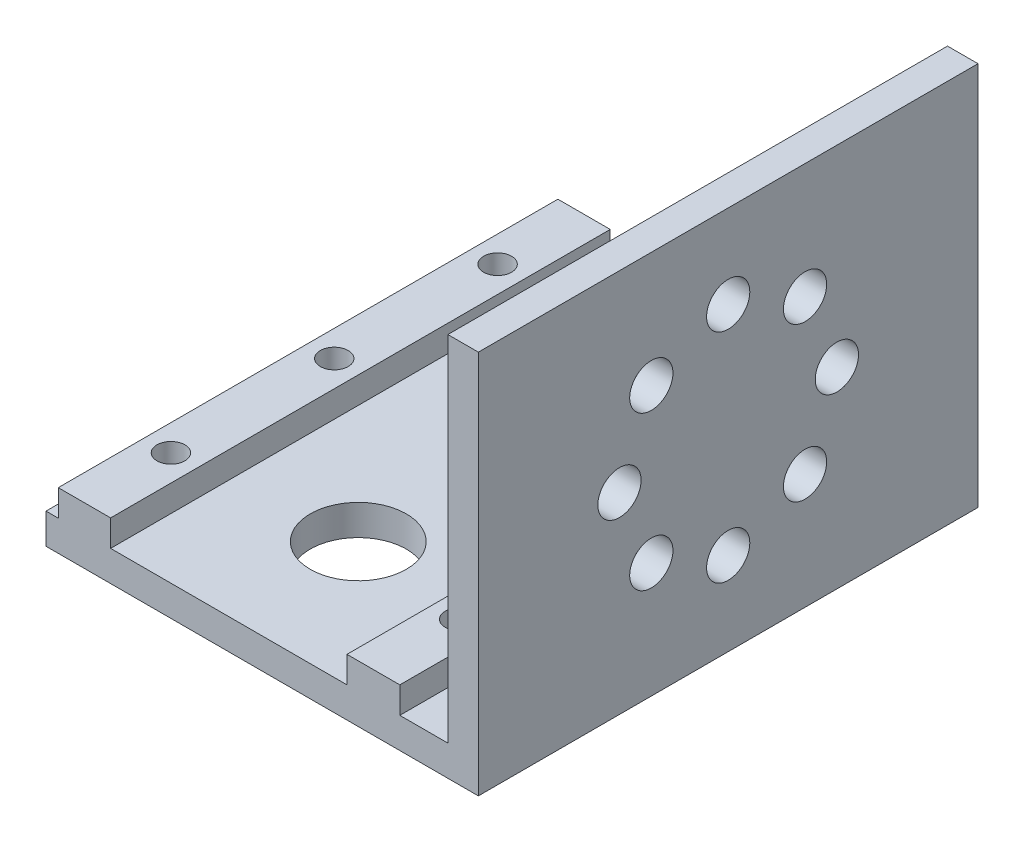
SolidWorks part; units mm, degrees
material "PLA"
ref_plane "Front Plane" through (0, 0, 0) normal (0, 0, 1) x (1, 0, 0)
ref_plane "Top Plane" through (0, 0, 0) normal (0, 1, 0) x (1, 0, 0)
ref_plane "Right Plane" through (0, 0, 0) normal (1, 0, 0) x (0, 0, -1)
sketch "Sketch1" plane through (0, 0, 0) normal (0, 0, 1) x (1, 0, 0)
  line L0 (0, 0) -> (0, 36.825)
  line L1 (0, 36.825) -> (3.175, 36.825)
  line L2 (3.175, 36.825) -> (3.175, -3.175)
  line L3 (3.175, -3.175) -> (-41.825, -3.175)
  line L4 (-41.825, -3.175) -> (-41.825, 0)
  line L5 (-41.825, 0) -> (0, 0) construction
  line L6 (-41.825, 0) -> (-40.55, 0)
  line L7 (-40.55, 0) -> (-40.55, 2.75)
  line L8 (-40.55, 2.75) -> (-35.1, 2.75)
  line L9 (-35.1, 2.75) -> (-35.1, 0)
  line L10 (-35.1, 0) -> (-10.5, 0)
  line L11 (-10.5, 0) -> (-10.5, 2.75)
  line L12 (-10.5, 2.75) -> (-5, 2.75)
  line L13 (-5, 2.75) -> (-5, 0)
  line L14 (-5, 0) -> (0, 0)
  line L15 (-40.55, 2.75) -> (-5, 2.75) construction
  line L16 (-37.825, 2.75) -> (-37.825, -3.175) construction
  dimension "D1" = 3.175
  dimension "D2" = 3.175
  dimension "D3" = 45
  dimension "D4" = 40
  dimension "D5" = 2.75
  dimension "D6" = 5.45
  dimension "D7" = 5.5
  dimension "D8" = 35.55
  dimension "D9" = 4
extrude "Boss-Extrude1" add sketch "Sketch1" along normal blind 52
sketch "Sketch2" plane through (3.175, 0, 0) normal (1, 0, 0) x (0, 0, -1)
  line L0 (-26, 36.825) -> (-26, -3.175) construction
  line L1 (-52, 36.825) -> (0, 36.825) construction
  line L2 (-52, -3.175) -> (0, -3.175) construction
  circle A0 centre (-26, 28.1387) radius 2
  circle A1 centre (-26, 16.825) radius 11.3137 construction
  circle A2 centre (-18, 24.825) radius 2
  circle A3 centre (-14.6863, 16.825) radius 2
  circle A4 centre (-18, 8.825) radius 2
  circle A5 centre (-26, 5.5113) radius 2
  circle A6 centre (-34, 8.825) radius 2
  circle A7 centre (-37.3137, 16.825) radius 2
  circle A8 centre (-34, 24.825) radius 2
  point P10 (0, 0)
  point P11 (0, 0)
  point P12 (-14.6863, 16.825)
  point P27 (-26, 16.825)
  dimension "D1" = 4
  dimension "D2" = 16
  dimension "D3" = 8
sketch "Sketch3" plane through (0, -3.175, 0) normal (0, -1, 0) x (-1, 0, 0)
  line L2 (41.825, 0) -> (-3.175, 0) construction
  line L3 (41.825, -52) -> (41.825, 0) construction
  circle A0 centre (7.825, -43) radius 1.25 construction
  circle A1 centre (37.825, -43) radius 1.25 construction
  circle A2 centre (37.825, -26) radius 1.25 construction
  circle A3 centre (37.825, -9) radius 1.25 construction
  circle A4 centre (7.825, -26) radius 1.25 construction
  circle A5 centre (7.825, -9) radius 1.25 construction
  circle A6 centre (22.825, -38.5) radius 5
  dimension "D1" = 2.5
  dimension "D6" = 10
  dimension "D7" = 4.5
  dimension "D2" = 9
  dimension "D3" = 4
  dimension "D8" = 15
  dimension "D4" = 2
  dimension "D5" = 3
extrude "Cut-Extrude2" cut sketch "Sketch3" against normal through all
hole_wizard "M2.5 Clearance Hole1" positions "Sketch4" profile "Sketch5" hole size "M2.5" standard "ISO" end condition through all
sketch "Sketch4" plane through (0, -3.175, 0) normal (0, -1, 0) x (-1, 0, 0)
  point P0 (7.825, -9)
  point P3 (37.825, -9)
  point P6 (7.825, -26)
  point P9 (37.825, -26)
  point P12 (37.825, -43)
  point P15 (7.825, -43)
sketch "Sketch5" plane through (-7.825, -3.175, 9) normal (1, 0, 0) x (0, 0, -1)
  line L0 (0, 0) -> (0, 40)
  line L1 (0, 40) -> (1.45, 40)
  line L2 (1.45, 40) -> (1.45, 0)
  line L5 (1.45, 0) -> (0, 0)
  line L11 (0, -6.35) -> (0, 107.95) construction
  dimension "Thru Hole Dia." = 2.9
  dimension "Thru Hole Depth" = 40
hole_wizard "M4 Clearance Hole1" positions "Sketch6" profile "Sketch7" hole size "M4" standard "ISO" end condition through all
sketch "Sketch6" plane through (3.175, 0, 0) normal (1, 0, 0) x (0, 0, -1)
  point P0 (-26, 28.1387)
  point P3 (-18, 24.825)
  point P6 (-14.6863, 16.825)
  point P9 (-18, 8.825)
  point P12 (-26, 5.5113)
  point P15 (-34, 8.825)
  point P18 (-37.3137, 16.825)
  point P21 (-34, 24.825)
sketch "Sketch7" plane through (3.175, 28.1387, 26) normal (0, 1, 0) x (0, 0, -1)
  line L0 (0, 0) -> (0, 45)
  line L1 (0, 45) -> (2.25, 45)
  line L2 (2.25, 45) -> (2.25, 0)
  line L5 (2.25, 0) -> (0, 0)
  line L11 (0, -6.35) -> (0, 107.95) construction
  dimension "Thru Hole Dia." = 4.5
  dimension "Thru Hole Depth" = 45
